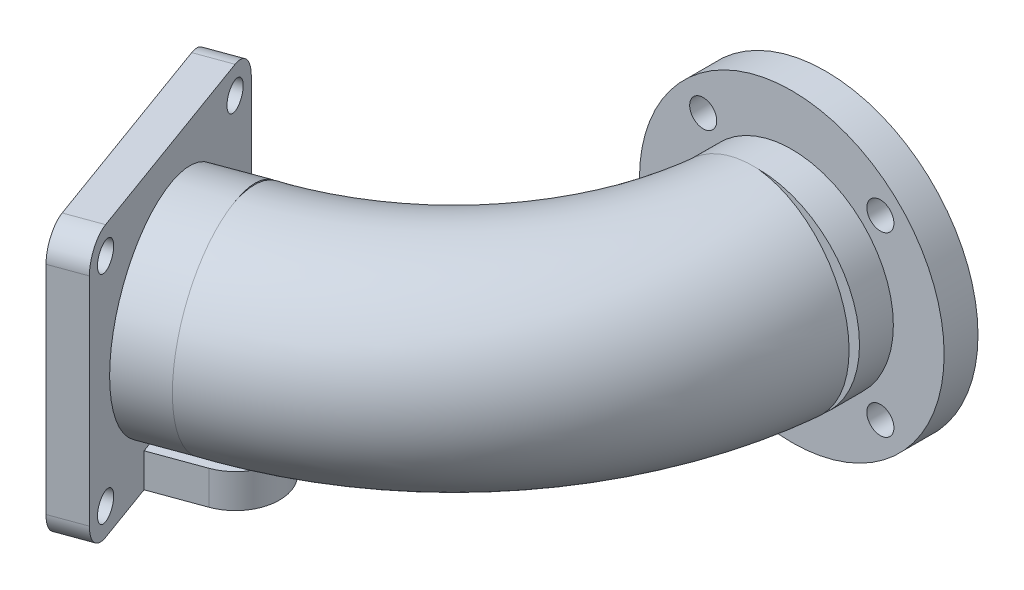
SolidWorks part; units mm, degrees
ref_plane "Front Plane" through (0, 0, 0) normal (0, 0, 1) x (1, 0, 0)
ref_plane "Top Plane" through (0, 0, 0) normal (0, 1, 0) x (1, 0, 0)
ref_plane "Right Plane" through (0, 0, 0) normal (1, 0, 0) x (0, 0, -1)
sketch "Sketch1" plane through (0, 0, 0) normal (0, 0, 1) x (1, 0, 0)
  line L0 (0, 0) -> (0, 29219.2699) construction
  line L1 (0, 0) -> (29219.2699, 0) construction
  line L2 (13.0815, 13.0815) -> (0, 0) construction
  circle A0 centre (0, 0) radius 15
  circle A1 centre (0, 0) radius 18.5 construction
  circle A2 centre (0, 0) radius 22.5
  circle A3 centre (13.0815, 13.0815) radius 2
  circle A4 centre (-13.0815, 13.0815) radius 2
  circle A5 centre (-13.0815, -13.0815) radius 2
  circle A6 centre (13.0815, -13.0815) radius 2
  dimension "D1" = 37
  dimension "D2" = 30
  dimension "D3" = 45
  dimension "D4" = 4
  dimension "D5" = 45
extrude "Boss-Extrude1" add sketch "Sketch1" along normal blind 5
extrude "Boss-Extrude2" add sketch "Sketch1<2>" along normal blind 10 and the other way blind 2.5 contours A0 region at (0, 0, 0)
sketch "Sketch1<2>" plane through (0, 0, 0) normal (0, 0, 1) x (1, 0, 0) same geometry as "Sketch1"
ref_plane "Plane1" through (0, 0, 10) normal (0, 0, 1) x (1, 0, 0)
sketch "Sketch2" plane through (0, 0, 10) normal (0, 0, 1) x (1, 0, 0)
  line L0 (-50, 66.4236) -> (-50, -75.9989) construction
  dimension "D1" = 50
ref_plane "Plane2" through (-47.365, 0, 17.2395) normal (-0.9397, 0, 0.342) x (0, -1, 0)
ref_plane "Plane3" through (-59.1112, 0, 21.5147) normal (-0.9397, 0, 0.342) x (0, -1, 0)
ref_axis "Axis1" through (-63.3022, -168.1075, 10) along (0, 1, 0)
sketch "Sketch4" plane through (-59.1112, 0, 21.5147) normal (-0.9397, 0, 0.342) x (0, -1, 0)
  line L0 (0, 0) -> (0, 50000) construction
  line L1 (0, 37.7463) -> (-50000, 37.7463) construction
  line L2 (168.1075, -12.2537) -> (-182.6601, -12.2537) construction
  line L4 (-16, 17.7463) -> (16, 17.7463)
  line L5 (-20, 21.7463) -> (-20, 53.7463)
  line L6 (-16, 57.7463) -> (16, 57.7463)
  line L7 (20, 21.7463) -> (20, 53.7463)
  line L8 (-20, 17.7463) -> (20, 57.7463) construction
  line L9 (-20, 57.7463) -> (20, 17.7463) construction
  circle A0 centre (0, 37.7463) radius 15
  circle A1 centre (16, 53.7463) radius 2
  circle A2 centre (-16, 53.7463) radius 2
  circle A3 centre (16, 21.7463) radius 2
  circle A4 centre (-16, 21.7463) radius 2
  arc A5 (-16, 17.7463) -> (-20, 21.7463) centre (-16, 21.7463) cw
  arc A6 (16, 17.7463) -> (20, 21.7463) centre (16, 21.7463) ccw
  arc A7 (16, 57.7463) -> (20, 53.7463) centre (16, 53.7463) cw
  arc A8 (-20, 53.7463) -> (-16, 57.7463) centre (-16, 53.7463) cw
  circle A9 centre (0, 37.7463) radius 10
  point P7 (0, 37.7463)
  dimension "D4" = 30
  dimension "D5" = 4
  dimension "D7" = 4
  dimension "D8" = 20
  dimension "D1" = 50
  dimension "D2" = 40
  dimension "D3" = 40
  dimension "D6" = 32
extrude "Boss-Extrude3" add sketch "Sketch4" against normal blind 5 separate body contours A8 L5 A5 L4 A6 L7 A7 L6 A4 A2 A1 A0 A3 region at (-52.5041, 18.4284, 39.6676)
extrude "Boss-Extrude4" add sketch "Sketch4<3>" against normal blind 12.5 contours A0 A9 | A9 region at (-46.2012, 14.5757, 56.9846) region at (-46.2012, 0, 56.9846)
sketch "Sketch4<3>" plane through (-59.1112, 0, 21.5147) normal (-0.9397, 0, 0.342) x (0, -1, 0) same geometry as "Sketch4"
sketch3d "3DSketch2"
  line L0 (0, 0, 5) -> (0, 0, 10) construction
  line L1 (-34.4551, 0, 52.7094) -> (-41.5028, 0, 55.2745) construction
  arc A0 (0, 0, 10) -> (-34.4551, 0, 52.7094) centre (-49.7603, 0, 5.1095) cw
  point P2 (-49.7603, -50, 5.1095)
  dimension "D1" = 50
sweep "Sweep3" add path "3DSketch2" circular profile diameter 30 parameters "D3"=30
sketch "Sketch22" plane through (0, -20, 0) normal (0, -1, 0) x (1, 0, 0)
  line L0 (-39.2796, 61.3825) -> (-32.2319, 58.8174)
  line L1 (-46.9751, 40.2394) -> (-36.0304, 70.3096) construction
  line L2 (-37.9595, 43.081) -> (-56.7706, -8.6021) construction
  line L3 (-32.2319, 58.8174) -> (-36.6782, 46.6014)
  line L4 (-36.6782, 46.6014) -> (-43.7259, 49.1665)
  line L5 (-46.6331, 41.1791) -> (-36.3724, 69.3699) construction
  line L6 (-43.7259, 49.1665) -> (-39.2796, 61.3825)
  line L7 (-29.5748, 66.8958) -> (-36.3724, 69.3699) construction
  circle A0 centre (-34.4551, 52.7094) radius 3
  circle A1 centre (-34.4551, 52.7094) radius 6.5
  point P6 (-41.5028, 55.2745)
  line M4 (-46.9751, 40.2394) -> (-36.0304, 70.3096)
  dimension "D3" = 6
  dimension "D1" = 13
  dimension "D2" = 15
extrude "Boss-Extrude5" add sketch "Sketch22" against normal blind 4.99 contours A1 L0 L4 M4 | L3 A1 A0 | L3 A1 A0 region at (-35.8198, -20, 59.924) region at (-31.4849, -20, 51.6283) region at (-37.4252, -20, 53.7904)
ref_plane "Plane4" through (-34.4551, -15, 52.7094) normal (0.3241, 0, 0.946) x (0.946, 0, -0.3241)
sketch "Sketch24" plane through (0, 0, 10) normal (0, 0, 1) x (1, 0, 0)
  circle A0 centre (0, 0) radius 10
  dimension "D1" = 20
revolve "Cut-Revolve1" cut sketch "Sketch24" angle 360 about L0
